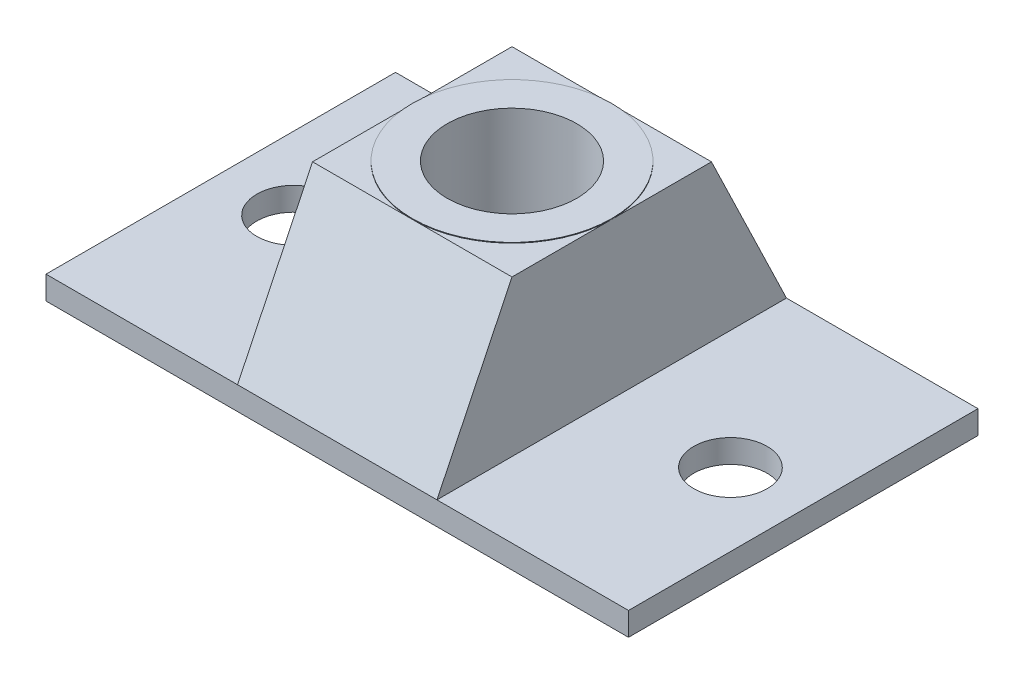
SolidWorks part; units mm, degrees
ref_plane "Front Plane" through (0, 0, 0) normal (0, 0, 1) x (1, 0, 0)
ref_plane "Top Plane" through (0, 0, 0) normal (0, 1, 0) x (1, 0, 0)
ref_plane "Right Plane" through (0, 0, 0) normal (1, 0, 0) x (0, 0, -1)
sketch "Sketch1" plane through (0, 0, 0) normal (0, 1, 0) x (1, 0, 0)
  line L0 (-25, 0) -> (8.56, 0) construction
  line L1 (-25, -15) -> (25, -15)
  line L2 (-25, -15) -> (-25, 15)
  line L3 (-25, 15) -> (25, 15)
  line L4 (25, -15) -> (25, 15)
  line L5 (-25, -15) -> (25, 15) construction
  line L6 (-25, 15) -> (25, -15) construction
  line L7 (8.56, 0) -> (0, 0) construction
  line L8 (0, 0) -> (-25, 0) construction
  line L9 (-12.5, 0) -> (-25, 0) construction
  line L10 (8.56, 0) -> (0, 0) construction
  line L11 (0, 0) -> (25, 0) construction
  line L12 (25, 0) -> (12.5, 0) construction
  circle A0 centre (0, 0) radius 5.56
  circle A1 centre (0, 0) radius 8.56
  circle A2 centre (-18.75, 0) radius 3.15
  circle A3 centre (18.75, 0) radius 3.15
  dimension "D1" = 3
  dimension "D2" = 17.12
  dimension "D3" = 11.12
  dimension "D4" = 50
  dimension "D5" = 30
extrude "Boss-Extrude1" add sketch "Sketch1" along normal blind 15.41 contours A1 A0 | A1 | A0 region at (-8.3179, 0, 0)
extrude "Boss-Extrude2" add sketch "Sketch1<3>" along normal blind 2 separate body contours L3 L4 L1 L2
sketch "Sketch1<3>" plane through (0, 0, 0) normal (0, 1, 0) x (1, 0, 0) same geometry as "Sketch1"
extrude "Cut-Extrude1" cut sketch "Sketch1<4>" along normal blind 2 contours A0
sketch "Sketch1<4>" plane through (0, 0, 0) normal (0, 1, 0) x (1, 0, 0) same geometry as "Sketch1"
extrude "Cut-Extrude2" cut sketch "Sketch1<5>" along normal blind 2 contours A2 | A3
sketch "Sketch1<5>" plane through (0, 0, 0) normal (0, 1, 0) x (1, 0, 0) same geometry as "Sketch1"
sketch "Sketch2" plane through (0, 2, 0) normal (0, 1, 0) x (1, 0, 0)
  line L0 (-8.56, 0) -> (-8.56, 15) construction
  line L1 (-25, 15) -> (25, 15) construction
  line L2 (-8.56, 15) -> (-8.56, -15) construction
  line L3 (-25, -15) -> (25, -15) construction
  line L4 (8.56, 0) -> (8.56, 15) construction
  line L5 (8.56, 15) -> (8.56, -15) construction
  line L6 (-8.56, 15) -> (8.56, 15)
  line L7 (8.56, 15) -> (8.56, -15)
  line L8 (8.56, -15) -> (-8.56, -15)
  line L9 (-8.56, -15) -> (-8.56, 15)
  circle A0 centre (0, 0) radius 8.56 construction
extrude "Boss-Extrude3" add sketch "Sketch2" along normal blind 13.35
sketch "Sketch3" plane through (0, 15.35, 0) normal (0, 1, 0) x (1, 0, 0)
  circle A0 centre (0, 0) radius 5.56
extrude "Cut-Extrude3" cut sketch "Sketch3" against normal blind 13.35
sketch "Sketch4" plane through (-8.56, 0, 0) normal (-1, 0, 0) x (0, 0, 1)
  line L0 (8.56, 15.35) -> (15, 2) construction
  line L1 (15, 2) -> (8.56, 2) construction
  line L2 (-15, 2) -> (15, 2) construction
  line L3 (8.56, 2) -> (8.56, 15.35) construction
  line L4 (8.56, 15.35) -> (-8.56, 15.35) construction
  line L5 (-8.56, 15.35) -> (-8.56, 2) construction
  line L6 (-8.56, 2) -> (-15, 2) construction
  line L7 (-15, 2) -> (-8.56, 15.35) construction
  line L8 (-8.56, 15.35) -> (-15, 15.35)
  line L9 (-15, 15.35) -> (-15, 2)
  line L10 (-15, 2) -> (-8.56, 15.35)
  line L11 (8.56, 15.35) -> (15, 15.35)
  line L12 (15, 15.35) -> (15, 2)
  line L13 (15, 2) -> (8.56, 15.35)
  line M1 (15, 15.35) -> (0, 15.35)
  line M5 (15, 2) -> (15, 15.35)
extrude "Cut-Extrude4" cut sketch "Sketch4" against normal blind 18.35 contours L13 M5 M1 | L10 L8 L9 region at (-8.56, 10.9, 12.8533)
